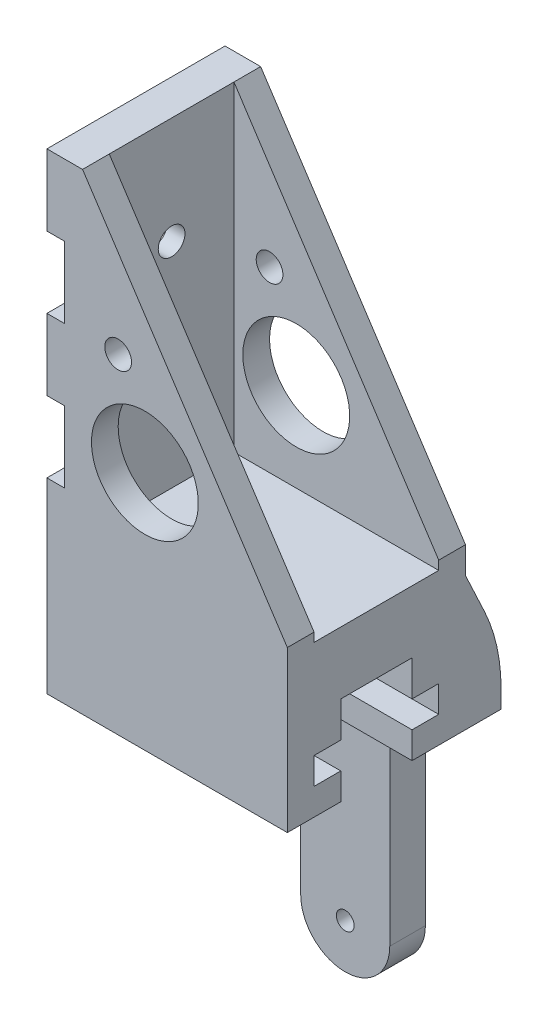
SolidWorks part; units mm, degrees
material "普通碳钢"
ref_plane "前视" through (0, 0, 0) normal (0, 0, 1) x (1, 0, 0)
ref_plane "上视" through (0, 0, 0) normal (0, 1, 0) x (1, 0, 0)
ref_plane "右视" through (0, 0, 0) normal (1, 0, 0) x (0, 0, -1)
sketch "草图1" plane through (0, 0, 0) normal (0, 0, 1) x (1, 0, 0)
  line L0 (0, 0) -> (2, 0)
  line L1 (2, 0) -> (25, -35)
  line L2 (25, -35) -> (25, -38)
  line L3 (25, -38) -> (0, -38)
  line L4 (0, -38) -> (0, 0)
  dimension "D1" = 38
  dimension "25" = 25
  dimension "D2" = 3
  dimension "D3" = 2
extrude "凸台-拉伸1" add sketch "草图1" along normal mid plane 20
shell "抽壳1" thickness 3 removed face at (13.5, -17.5, 0)
sketch "草图2" plane through (0, 0, 0) normal (0, 0, 1) x (1, 0, 0)
  line L0 (2, 0) -> (2, -36)
  line L1 (2, 0) -> (0, 0) construction
  line L2 (2, -36) -> (25, -36)
  line L3 (25, -38) -> (25, -35) construction
  line L4 (25, -36) -> (25, -35)
  line L5 (25, -35) -> (22, -30.4348)
  line L6 (22, -30.4348) -> (22, -35)
  line L7 (22, -35) -> (22, -30.4348) construction
  line L8 (3, -35) -> (22, -35) construction
  line L9 (22, -35) -> (3, -35)
  line L10 (3, -35) -> (3, -3)
  line L11 (3, -3) -> (3.9714, -3)
  line L12 (3.9714, -3) -> (2, 0)
  line L13 (0, -38) -> (25, -38) construction
  dimension "D1" = 2
extrude "切除-拉伸1" cut sketch "草图2" against normal mid plane 14
sketch "草图3" plane through (0, 0, 0) normal (0, 0, 1) x (1, 0, 0)
  line L1 (0, 0) -> (0, -38) construction
  line L2 (0, 0) -> (-2, 0)
  line L3 (0, 0) -> (0, -8)
  line L4 (0, -8) -> (-2, -8)
  line L5 (-2, 0) -> (-2, -8)
  line L6 (0, -16) -> (-2, -16)
  line L7 (0, -16) -> (0, -24)
  line L8 (0, -24) -> (-2, -24)
  line L9 (-2, -16) -> (-2, -24)
  line L10 (0, -38) -> (25, -38) construction
  line L11 (0, -32) -> (-2, -32)
  line L12 (0, -32) -> (0, -38)
  line L13 (0, -38) -> (-2, -38)
  line L14 (-2, -32) -> (-2, -38)
  dimension "D1" = 2
  dimension "D2" = 6
  dimension "D3" = 8
  dimension "D4" = 8
  dimension "D5" = 8
extrude "凸台-拉伸2" add sketch "草图3" along normal mid plane 20
sketch "草图4" plane through (0, 0, -10) normal (0, 0, -1) x (-1, 0, 0)
  line L0 (2, -38) -> (-25, -38) construction
  line L1 (0, -24) -> (0, -32) construction
  line L2 (0, -8) -> (0, -16) construction
  circle A0 centre (-9, -26) radius 6
  circle A1 centre (-6, -16) radius 1.5
  dimension "D1" = 12
  dimension "D2" = 3
  dimension "D3" = 12
  dimension "D4" = 9
  dimension "D5" = 22
  dimension "D6" = 6
extrude "切除-拉伸2" cut sketch "草图4" against normal blind 20
sketch "草图5" plane through (0, 0, 0) normal (-1, 0, 0) x (0, 0, 1)
  line L0 (0, 0) -> (0, -38) construction
  line L1 (10, -38) -> (-10, -38) construction
  line L2 (-10, -12) -> (10, -12) construction
  line L3 (-10, -8) -> (-10, -16) construction
  line L4 (10, -8) -> (10, -16) construction
  line L5 (-10, -28) -> (10, -28) construction
  line L6 (-10, -24) -> (-10, -32) construction
  line L7 (10, -24) -> (10, -32) construction
  circle A0 centre (0, -12) radius 1.5
  circle A1 centre (0, -28) radius 1.5
  dimension "D1" = 3
extrude "切除-拉伸3" cut sketch "草图5" against normal blind 20
sketch "草图6" plane through (25, 0, 0) normal (1, 0, 0) x (0, 0, -1)
  line L0 (-10, -38) -> (-10, -53)
  line L1 (-10, -38) -> (10, -38)
  line L2 (10, -38) -> (12.1176, -42.5294)
  line L3 (14, -51) -> (14, -53)
  line L4 (14, -53) -> (4, -53)
  line L7 (4, -50) -> (4, -53)
  line L8 (7, -50) -> (4, -50)
  line L9 (7, -47) -> (7, -50)
  line L10 (4, -47) -> (7, -47)
  line L11 (4, -43) -> (4, -47)
  line L12 (-4, -43) -> (4, -43)
  line L13 (-4, -43) -> (-4, -47)
  line L14 (-4, -47) -> (-7, -47)
  line L15 (-7, -47) -> (-7, -50)
  line L16 (-7, -50) -> (-4, -50)
  line L17 (-4, -50) -> (-4, -53)
  line L18 (-4, -53) -> (-10, -53)
  line L22 (0, -38) -> (0, -52.3559) construction
  arc A0 (14, -51) -> (12.1176, -42.5294) centre (-6, -51) ccw
  dimension "D8" = 20
  dimension "D1" = 15
  dimension "D2" = 3
  dimension "D3" = 3
  dimension "D4" = 4
  dimension "D5" = 6
  dimension "D6" = 3
  dimension "D7" = 6
  dimension "D9" = 10
  dimension "D10" = 2
extrude "凸台-拉伸3" add sketch "草图6" against normal up to surface (27 mm away) up to face at (-2, -35, 0)
sketch "草图7" plane through (0, 0, -14) normal (0, 0, -1) x (-1, 0, 0)
  line L0 (-11.5, -53) -> (-11.5, -73) construction
  line L1 (2, -53) -> (-25, -53) construction
  line L2 (-6.5, -53) -> (-6.5, -73)
  line L3 (-16.5, -53) -> (-16.5, -73)
  line L4 (-16.5, -53) -> (-6.5, -53)
  circle A0 centre (-11.5, -73) radius 1
  arc A1 (-16.5, -73) -> (-6.5, -73) centre (-11.5, -73) ccw
  point P4 (-11.5, -53)
  dimension "D2" = 25
  dimension "D3" = 2
  dimension "D1" = 10
extrude "凸台-拉伸4" add sketch "草图7" against normal blind 4
sketch "草图8" plane through (0, 0, -14) normal (0, 0, -1) x (-1, 0, 0)
  line L0 (-16.5, -73) -> (-16.5, -78.3)
  line L1 (-6.5, -73) -> (-6.5, -78.3)
  arc A0 (-16.5, -78.3) -> (-6.5, -78.3) centre (-11.5, -78.3) ccw
  arc A1 (-16.5, -73) -> (-6.5, -73) centre (-11.5, -73) ccw
extrude "凸台-拉伸5" add sketch "草图8" against normal blind 4
sketch "草图9" plane through (0, 0, -14) normal (0, 0, -1) x (-1, 0, 0)
  circle A0 centre (-11.5, -73) radius 1
extrude "凸台-拉伸6" add sketch "草图9" against normal blind 4
sketch "草图10" plane through (0, 0, -14) normal (0, 0, -1) x (-1, 0, 0)
  circle A0 centre (-11.5, -78.3) radius 1
extrude "切除-拉伸4" cut sketch "草图10" against normal blind 4
